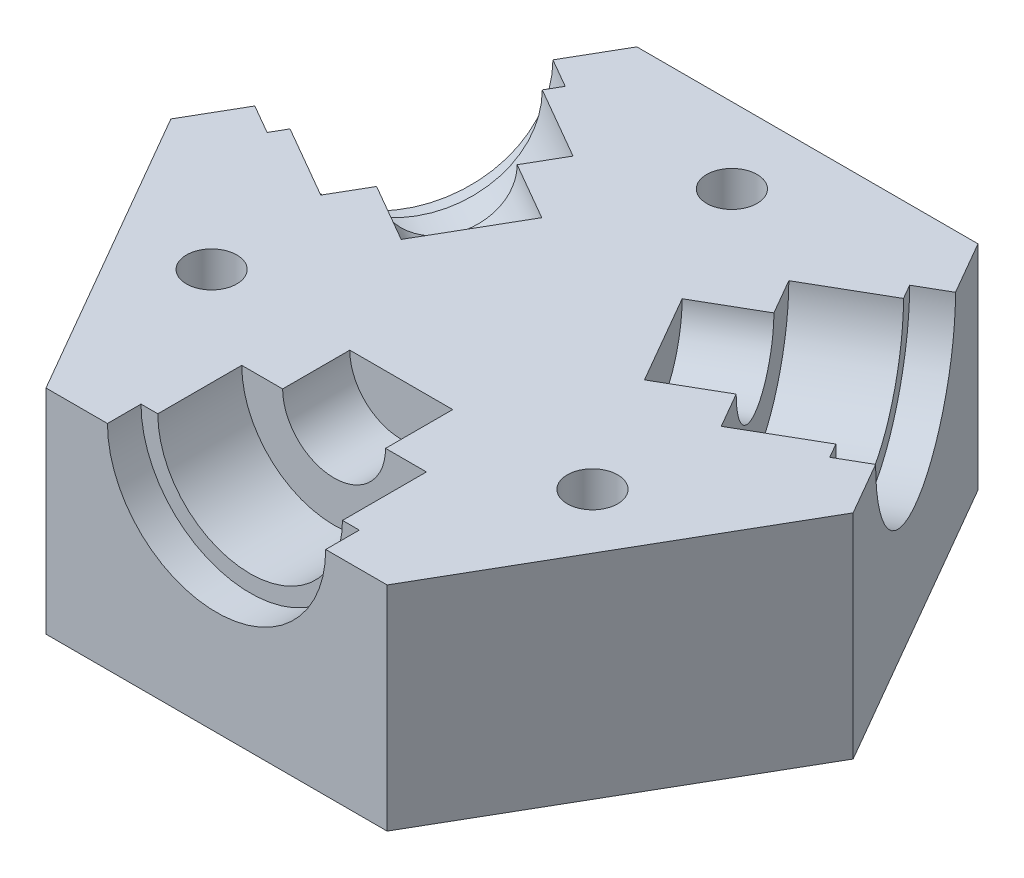
SolidWorks part; units mm, degrees
ref_plane "Front Plane" through (0, 0, 0) normal (0, 0, 1) x (1, 0, 0)
ref_plane "Top Plane" through (0, 0, 0) normal (0, 1, 0) x (1, 0, 0)
ref_plane "Right Plane" through (0, 0, 0) normal (1, 0, 0) x (0, 0, -1)
sketch "Sketch1" plane through (0, 0, 0) normal (0, 1, 0) x (1, 0, 0)
  line L1 (10.16, -17.5976) -> (20.32, 0)
  line L2 (20.32, 0) -> (10.16, 17.5976)
  line L3 (10.16, 17.5976) -> (-10.16, 17.5976)
  line L4 (-10.16, 17.5976) -> (-20.32, 0)
  line L5 (-20.32, 0) -> (-10.16, -17.5976)
  line L6 (-10.16, -17.5976) -> (10.16, -17.5976)
  circle A0 centre (0, 0) radius 17.5976 construction
  point P1 (0, 0)
  point P10 (0, 0)
  dimension "D1" = 20.32
extrude "Boss-Extrude1" add sketch "Sketch1" along normal blind 12.7 contours L4 L5 L6 L1 L2 L3
sketch "Sketch5" plane through (0, 12.7, 0) normal (0, 1, 0) x (1, 0, 0)
  line L14 (0, -17.5976) -> (0, -6.5976)
  line L15 (-10.16, -17.5976) -> (10.16, -17.5976) construction
  line L16 (0, -6.5976) -> (-3.0653, -6.5976)
  line L17 (-3.0653, -6.5976) -> (-3.0653, -10.5976)
  line L18 (-3.0653, -10.5976) -> (-5.5, -10.5976)
  line L19 (-5.5, -10.5976) -> (-5.5, -15.5976)
  line L20 (-5.5, -15.5976) -> (-6.5, -15.5976)
  line L21 (-6.5, -15.5976) -> (-6.5, -17.5976)
  line L22 (-6.5, -17.5976) -> (0, -17.5976)
  dimension "D1" = 6.5
  dimension "D2" = 5.5
  dimension "D3" = 2
  dimension "D4" = 5
  dimension "D5" = 4
  dimension "D6" = 3.0653
revolve "Cut-Revolve1" cut sketch "Sketch5" angle 360 about L14
ref_axis "Axis1" through (0, -0.635, 0) along (0, 1, 0)
pattern_circular "CirPattern1" count 3 over 360 about axis through (0, -0.635, 0) along (0, 1, 0) of "Cut-Revolve1"
sketch "Sketch7" plane through (0, 12.7, 0) normal (0, 1, 0) x (1, 0, 0)
  line L0 (10.16, 17.5976) -> (-10.16, 17.5976) construction
  line L1 (-20.32, 0) -> (-10.16, -17.5976) construction
  line L2 (10.16, -17.5976) -> (20.32, 0) construction
  circle A0 centre (0, 13.0976) radius 1.5
  circle A1 centre (11.3429, -6.5488) radius 1.5
  circle A2 centre (-11.3429, -6.5488) radius 1.5
  point P11 (0, 0)
  dimension "D1" = 3
  dimension "D2" = 3
  dimension "D4" = 3
  dimension "D5" = 3
  dimension "D3" = 3
extrude "Cut-Extrude2" cut sketch "Sketch7" against normal blind 6.35
